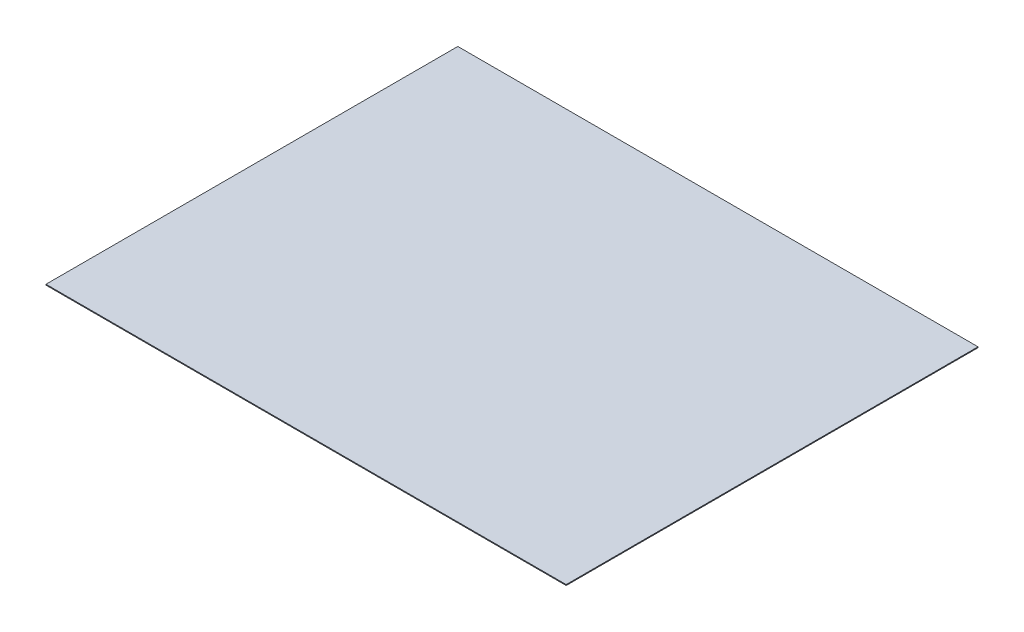
SolidWorks part; units mm, degrees
note: The reader was unsure of these and kept them because the rebuilt part matched: thickness of "Base-Flange1".
material "AISI 304"
ref_plane "Front Plane" through (0, 0, 0) normal (0, 0, 1) x (1, 0, 0)
ref_plane "Top Plane" through (0, 0, 0) normal (0, 1, 0) x (1, 0, 0)
ref_plane "Right Plane" through (0, 0, 0) normal (1, 0, 0) x (0, 0, -1)
sketch "Sketch1" plane through (0, 0, 0) normal (0, 1, 0) x (1, 0, 0)
  line L0 (-600, -475) -> (600, -475)
  line L2 (600, -475) -> (600, 475)
  line L3 (600, 475) -> (-600, 475)
  line L4 (-600, -475) -> (-600, 475)
  line L5 (600, -475) -> (-600, 475) construction
  line L6 (600, 475) -> (-600, -475) construction
  point P0 (0, 0)
  dimension "D1" = 1200
  dimension "D2" = 950
base flange "Base-Flange1" sketch "Sketch1" thickness 2 reverse thickness direction no parameters "D1"=0.7366
sketch "Bend-Lines1" [suppressed] plane through (0, 0, 0) normal (0, 1, 0) x (1, 0, 0)
sketch "Bounding-Box1" [suppressed] plane through (0, 0, 0) normal (0, 1, 0) x (1, 0, 0)
sheet metal parameters "Sheet-Metal1" thickness 2 parameters "D1"=0.7366
flat pattern "Flat-Pattern1" [suppressed]
sketch "Bend-Lines2" plane through (0, 0, 0) normal (0, 1, 0) x (1, 0, 0)
sketch3d "Bounding-Box2" [suppressed]
  line L0 (600, -475, 0) -> (-600, -475, 0) construction
  line L1 (600, 475, 0) -> (-600, 475, 0) construction
  line L2 (600, -475, 0) -> (600, 475, 0) construction
  line L3 (-600, -475, 0) -> (-600, 475, 0) construction
equation "\"thickness 1\" = 2"
equation "\"thickness 2\"= 3"
equation "\"connecting flange\"= 35"
equation "\"main length\"= 1200"
equation "\"main width\"= 1200"
equation "\"divider panel distance offset\"= 296"
equation "\"top panel slot length\"= 250"
equation "\"top panel slot width\"= 700"
equation "\"side panel length\"= 1200"
equation "\"side panel width\"= 950"
equation "\"access hatch length\" = \"access hatch cutout length\" + \"access hatch offset\" * 2"
equation "\"access hatch width\" = \"access hatch cutout width\" + \"access hatch offset\" * 2"
equation "\"access hatch offset X\"= 100"
equation "\"access hatch offset Y\"= 100"
equation "\"back panel access hatch length\"= 1150"
equation "\"back panel access hatch width\"= 206"
equation "\"back panel access hatch flange\"= 40"
equation "\"slotted panel length\" = \"main length\" + 100"
equation "\"slotted panel width\" = \"main width\""
equation "\"slot count x\"= 4"
equation "\"slot count y\"= 9"
equation "\"slot offset\" = \"water tray depth\""
equation "\"slot length\"= 30"
equation "\"slot width\"= 200"
equation "\"slot offset x\" = \"slot length\" + \"slot offset\""
equation "\"slot offset y\" = \"slot width\" + \"slot offset\""
equation "\"drift eliminator size offset\"= 5"
equation "\"drift eliminator length\"= \"back panel access hatch length\" - \"drift eliminator size offset\""
equation "\"drift eliminator width\"= \"back panel access hatch width\" - \"drift eliminator size offset\""
equation "\"drift eliminator depth\" = \"divider panel distance offset\""
equation "\"guide rail flange\"= 40"
equation "\"guid rail flange mount side\"= 20"
equation "\"guid rail back length\" = \"main width\" - \"guide rail flange\" * 2"
equation "\"splash plate length\"= 400"
equation "\"splash plate width\" = \"main width\""
equation "\"splash plate air gap\"= 200"
equation "\"splash plate slot count\"= 11"
equation "\"splash plate slot length\"= 50"
equation "\"splash plate slot height\"= 50"
equation "\"splash plate slot offset\"= 65"
equation "\"water tray depth\"= 150"
equation "\"water tray width\"= 200"
equation "\"dimpled panel length\" = \"main length\" - 200 - \"water tray depth\"/2"
equation "\"dimpled panel top offset\" = \"water tray depth\"/2"
equation "\"dimpled panel width\" = \"main width\""
equation "\"dimple panel slot count\"= 36"
equation "\"dimple panel slot length\"= 8"
equation "\"dimple panel slot width\"= 8"
equation "\"dimple panel slot offset\"= 25"
equation "\"sump base flat section width\"= 300"
equation "\"sump upper depth\"= 300"
equation "\"sump depth\"= 550"
equation "\"D1@Sketch1\"=\"main width\""
equation "\"D2@Sketch1\"=\"side panel width\""
equation "\"D7@Sheet-Metal1\"=\"thickness 1\""
